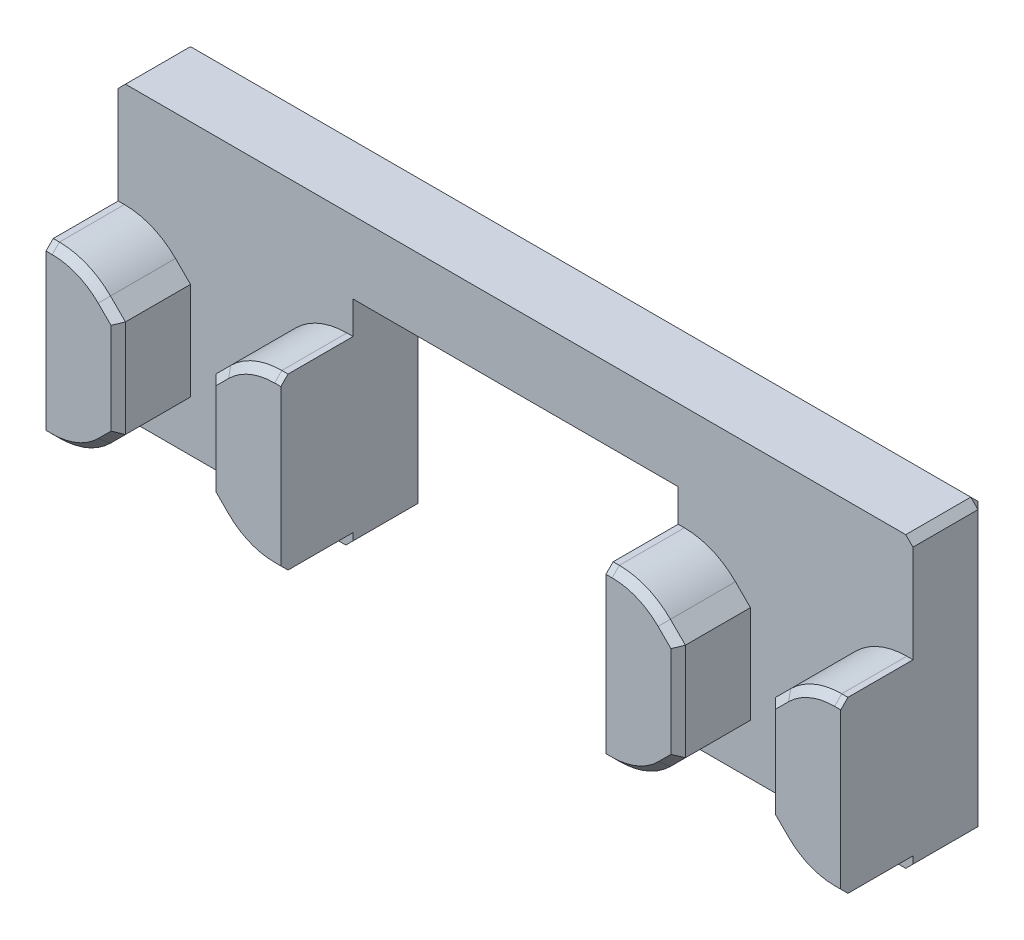
SolidWorks part; units mm, degrees
ref_plane "Front" through (0, 0, 0) normal (0, 0, 1) x (1, 0, 0)
ref_plane "Top" through (0, 0, 0) normal (0, 1, 0) x (1, 0, 0)
ref_plane "Right" through (0, 0, 0) normal (1, 0, 0) x (0, 0, -1)
sketch "Sketch1" plane through (0, 0, 0) normal (0, 0, 1) x (1, 0, 0)
  line L0 (-11, 4) -> (11, 4)
  line L5 (11, 4) -> (11, -4)
  line L6 (11, -4) -> (4.5, -4)
  line L7 (4.5, -4) -> (4.5, 2)
  line L8 (4.5, 2) -> (-4.5, 2)
  line L9 (-4.5, 2) -> (-4.5, -4)
  line L10 (-4.5, -4) -> (-11, -4)
  line L11 (-11, -4) -> (-11, 4)
  line L12 (4.5, -4) -> (11, -4) construction
  line L13 (10.8, 4) -> (-10.8, 4) construction
extrude "Boss-Extrude1" add sketch "Sketch1" against normal blind 2
sketch "Sketch2" plane through (0, 0, 0) normal (0, 0, 1) x (1, 0, 0)
  line L0 (11, 4) -> (11, -4) construction
  line L1 (11, 1.1) -> (11, -3.6)
  line L20 (13.5, -2.6) -> (13.5, 0.1)
  line L22 (13.5, 0.1) -> (13.0858, 0.5142)
  line L24 (11.6716, 1.1) -> (10.8284, 1.1)
  line L25 (11, 1.1) -> (10.8284, 1.1)
  line L26 (9.4142, 0.5142) -> (9, 0.1)
  line L27 (9.4142, 0.5142) -> (9, 0.1)
  line L28 (9, 0.1) -> (9, -2.6)
  line L29 (9, 0.1) -> (9, -2.6)
  line L30 (9, -2.6) -> (9.4142, -3.0142)
  line L31 (9, -2.6) -> (9.4142, -3.0142)
  line L32 (10.8284, -3.6) -> (11.6716, -3.6)
  line L33 (10.8284, -3.6) -> (11, -3.6)
  line L34 (13.0858, -3.0142) -> (13.5, -2.6)
  line L36 (13.4, -2.5586) -> (13.4, 0.0586)
  line L38 (13.4, 0.0586) -> (13.0151, 0.4435)
  line L40 (11.6716, 1) -> (10.8284, 1)
  line L41 (11, 1) -> (10.8284, 1) construction
  line L42 (9.4849, 0.4435) -> (9.1, 0.0586)
  line L43 (9.4849, 0.4435) -> (9.1, 0.0586) construction
  line L44 (9.1, 0.0586) -> (9.1, -2.5586)
  line L45 (9.1, 0.0586) -> (9.1, -2.5586) construction
  line L46 (9.1, -2.5586) -> (9.4849, -2.9435)
  line L47 (9.1, -2.5586) -> (9.4849, -2.9435) construction
  line L48 (10.8284, -3.5) -> (11.6716, -3.5)
  line L49 (10.8284, -3.5) -> (11, -3.5) construction
  line L50 (13.0151, -2.9435) -> (13.4, -2.5586)
  arc A18 (13.0858, 0.5142) -> (11.6716, 1.1) centre (11.6716, -0.9) ccw
  arc A20 (10.8284, 1.1) -> (9.4142, 0.5142) centre (10.8284, -0.9) ccw
  arc A21 (10.8284, 1.1) -> (9.4142, 0.5142) centre (10.8284, -0.9) ccw
  arc A22 (9.4142, -3.0142) -> (10.8284, -3.6) centre (10.8284, -1.6) ccw
  arc A23 (9.4142, -3.0142) -> (10.8284, -3.6) centre (10.8284, -1.6) ccw
  arc A24 (11.6716, -3.6) -> (13.0858, -3.0142) centre (11.6716, -1.6) ccw
  arc A26 (13.0151, 0.4435) -> (11.6716, 1) centre (11.6716, -0.9) ccw
  arc A28 (10.8284, 1) -> (9.4849, 0.4435) centre (10.8284, -0.9) ccw
  arc A29 (10.8284, 1) -> (9.4849, 0.4435) centre (10.8284, -0.9) ccw construction
  arc A30 (9.4849, -2.9435) -> (10.8284, -3.5) centre (10.8284, -1.6) ccw
  arc A31 (9.4849, -2.9435) -> (10.8284, -3.5) centre (10.8284, -1.6) ccw construction
  arc A32 (11.6716, -3.5) -> (13.0151, -2.9435) centre (11.6716, -1.6) ccw
  dimension "D1" = 0
  dimension "D2" = 0.1
extrude "Boss-Extrude2" add sketch "Sketch2" along normal blind 2 contours L31 A23 L33 L1 L25 A21 L27 L29 | L25 A21 L27 L29 L31 A23 L33 L1 region at (10.9489, 1.05, 0)
ref_plane "Plane1" through (7.75, 0, 0) normal (1, 0, 0) x (0, 0, -1)
mirror "Mirror1" about plane through (7.75, 0, 0) normal (1, 0, 0) of "Boss-Extrude2"
mirror "Mirror2" about plane through (0, 0, 0) normal (1, 0, 0) of "Mirror1"
chamfer "Deburs" distance 0.2 angle 45 42 edges at (0, 4, -2) (11, 4, -1) (11, 0, -2) (11, -4, -1) (7.75, -4, -2) (4.5, -4, -1) (4.5, -1, -2) (0, 2, -2) (-4.5, -1, -2) (-4.5, -4, -1) (-7.75, -4, -2) (-11, 4, -1) (-11, 0, -2) (-11, -4, -1) (10.9142, 1.1, 2) (10.0631, 0.9478, 2) (9.2071, 0.3071, 2) (9, -1.25, 2) (9.2071, -2.8071, 2) (10.9142, -3.6, 2) (10.0631, -3.4478, 2) (4.5858, 1.1, 2) (6.2929, 0.3071, 2) (5.4369, 0.9478, 2) (6.5, -1.25, 2) (6.2929, -2.8071, 2) (4.5858, -3.6, 2) (5.4369, -3.4478, 2) (-10.9142, 1.1, 2) (-9.2071, 0.3071, 2) (-10.0631, 0.9478, 2) (-4.5858, 1.1, 2) (-6.2929, 0.3071, 2) (-5.4369, 0.9478, 2) (-4.5858, -3.6, 2) (-5.4369, -3.4478, 2) (-6.5, -1.25, 2) (-6.2929, -2.8071, 2) (-9, -1.25, 2) (-9.2071, -2.8071, 2) (-10.9142, -3.6, 2) (-10.0631, -3.4478, 2)
